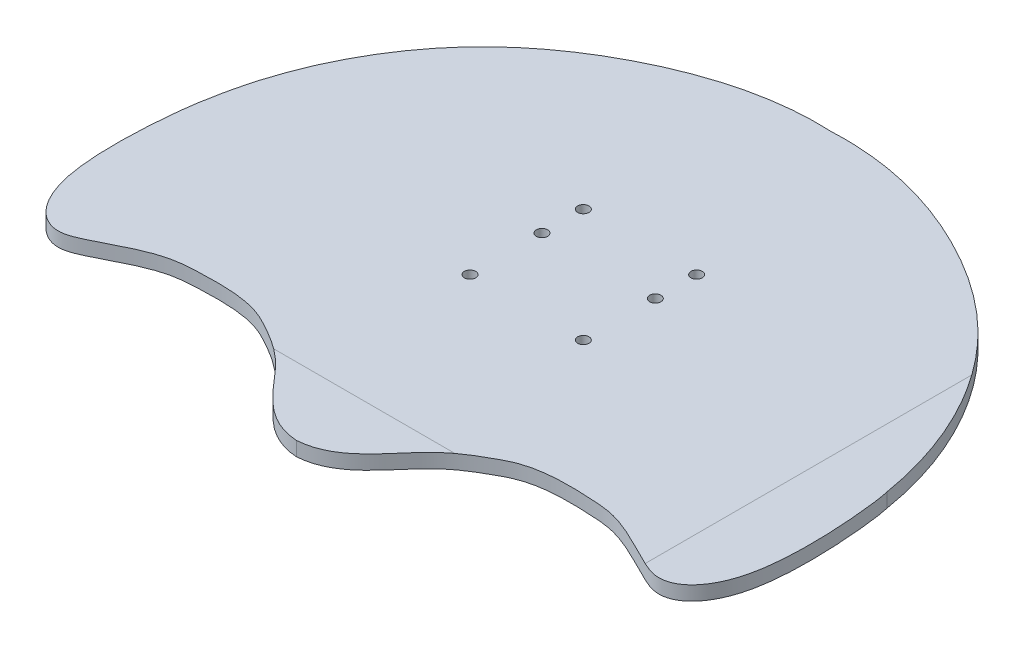
SolidWorks part; units mm, degrees
material "6061-T6 (SS)"
ref_plane "Front Plane" through (0, 0, 0) normal (0, 0, 1) x (1, 0, 0)
ref_plane "Top Plane" through (0, 0, 0) normal (0, 1, 0) x (1, 0, 0)
ref_plane "Right Plane" through (0, 0, 0) normal (1, 0, 0) x (0, 0, -1)
sketch "Sketch3" plane through (0, 0, 0) normal (0, 1, 0) x (1, 0, 0)
  line L0 (0, 0) -> (0, 159.1899) construction
  line L1 (0, 0) -> (0, -140.5301) construction
  line L2 (0, 0) -> (-190.5, 0) construction
  line L3 (0, 0) -> (190.5, 0) construction
  spline S0 degree 3 poles (-190.5, 0) (-184.3927, 37.537) (-157.2613, 93.9641) (-82.3875, 146.6227) (-31.3114, 160.7999) (0, 159.1899) knots 0 0 0 0 0.424401 0.65637 1 1 1 1
  spline S1 degree 3 poles (-190.5, 0) (-192.064, -4.9635) (-201.9672, -83.3146) (-174.6966, -109.29) (-151.6301, -100.568) (-131.4108, -87.7198) (-96.8436, -85.3754) (-78.6925, -86.2588) (-58.8335, -96.8794) (-37.3059, -109.9358) (-21.3496, -139.1148) (0, -140.5301) knots 0 0 0 0 0.166997 0.292321 0.319633 0.426735 0.458914 0.609242 0.64191 0.766802 1 1 1 1
  spline S2 degree 3 poles (190.5, 0) (192.064, -4.9635) (201.9672, -83.3146) (174.6966, -109.29) (151.6301, -100.568) (131.4108, -87.7198) (96.8436, -85.3754) (78.6925, -86.2588) (58.8335, -96.8794) (37.3059, -109.9358) (21.3496, -139.1148) (0, -140.5301) knots 0 0 0 0 0.166997 0.292321 0.319633 0.426735 0.458914 0.609242 0.64191 0.766802 1 1 1 1
  spline S3 degree 3 poles (190.5, 0) (184.3927, 37.537) (157.2613, 93.9641) (82.3875, 146.6227) (31.3114, 160.7999) (0, 159.1899) knots 0 0 0 0 0.424401 0.65637 1 1 1 1
  dimension "D1" = 381
  dimension "D2" = 299.72
  dimension "D3" = 159.1899
  dimension "D4" = 86.8953
  dimension "D5" = 104.4979
  dimension "D6" = 29.1616
  dimension "D7" = 92.2742
  dimension "D8" = 108.411
  dimension "D9" = 67.4883
  dimension "D10" = 43.7314
  dimension "D11" = 117.6915
  dimension "D12" = 162.2568
  dimension "D13" = 89.4522
  dimension "D14" = 140.1036
  dimension "D15" = 175.0666
  dimension "D16" = 50.2669
  dimension "D17" = 101.3666
  dimension "D18" = 138.1225
  dimension "D19" = 155.1557
  dimension "D20" = 192.0074
  dimension "D21" = 193.9268
  dimension "D23" = 76.6666
extrude "Boss-Extrude1" add sketch "Sketch3" along normal blind 7.9502 from surface starting at plane "Top Plane"
sketch "Sketch5" plane through (0, 0, 0) normal (0, -1, 0) x (1, 0, 0)
  line L0 (0, 0) -> (0, -20.32) construction
  line L1 (31.75, -52.07) -> (-31.75, -52.07)
  line L2 (31.75, -52.07) -> (31.75, 11.43)
  line L3 (31.75, 11.43) -> (-31.75, 11.43)
  line L4 (-31.75, -52.07) -> (-31.75, 11.43)
  line L5 (31.75, -52.07) -> (-31.75, 11.43) construction
  line L6 (31.75, 11.43) -> (-31.75, -52.07) construction
  line L7 (-31.75, -52.07) -> (-31.75, -28.8925)
  line L8 (-31.75, -28.8925) -> (31.75, -28.8925) construction
  point P0 (0, -20.32)
  point P3 (0, -20.32)
  dimension "D2" = 63.5
  dimension "D3" = 63.5
  dimension "D4" = 23.1775
hole_wizard "1/4 (0.25) Diameter Hole1" positions "Sketch6" profile "Sketch7" hole size "1/4" standard "ANSI Inch" end condition through all
sketch "Sketch6" plane through (0, 0, 0) normal (0, -1, 0) x (-1, 0, 0)
  point P0 (-31.75, 52.07)
  point P3 (31.75, 52.07)
  point P6 (31.75, -11.43)
  point P9 (-31.75, -11.43)
  point P12 (-31.75, 28.8925)
  point P15 (31.75, 28.8925)
sketch "Sketch7" plane through (31.75, 0, -52.07) normal (1, 0, 0) x (0, 0, -1)
  line L0 (0, 0) -> (0, 7.9502)
  line L1 (0, 7.9502) -> (3.175, 7.9502)
  line L2 (3.175, 7.9502) -> (3.175, 0)
  line L5 (3.175, 0) -> (0, 0)
  line L11 (0, -6.35) -> (0, 107.95) construction
  dimension "Thru Hole Dia." = 6.35
  dimension "Thru Hole Depth" = 7.9502
sketch "Sketch9" plane through (0, 7.9502, 0) normal (0, 1, 0) x (1, 0, 0)
  line L0 (157.5201, -102.5466) -> (157.5201, 80.5195)
  line L1 (-50.7649, -102.4301) -> (50.7649, -102.4301)
  spline S0 degree 3 poles (0, -140.5301) (21.3496, -139.1148) (37.3059, -109.9358) (58.8335, -96.8794) (78.6925, -86.2588) (96.8436, -85.3754) (131.4108, -87.7198) (151.6301, -100.568) (174.6966, -109.29) (201.9672, -83.3146) (192.064, -4.9635) (190.5, 0) knots 0 0 0 0 0.233198 0.35809 0.390758 0.541086 0.573265 0.680367 0.707679 0.833003 1 1 1 1 construction
  spline S1 degree 3 poles (190.5, 0) (184.3927, 37.537) (157.2613, 93.9641) (82.3875, 146.6227) (31.3114, 160.7999) (0, 159.1899) knots 0 0 0 0 0.424401 0.65637 1 1 1 1 construction
  spline S2 degree 3 poles (-190.5, 0) (-192.064, -4.9635) (-201.9672, -83.3146) (-174.6966, -109.29) (-151.6301, -100.568) (-131.4108, -87.7198) (-96.8436, -85.3754) (-78.6925, -86.2588) (-58.8335, -96.8794) (-37.3059, -109.9358) (-21.3496, -139.1148) (0, -140.5301) knots 0 0 0 0 0.166997 0.292321 0.319633 0.426735 0.458914 0.609242 0.64191 0.766802 1 1 1 1 construction
  dimension "D1" = 38.1
split line "Split Line1"
equation "\"Plate thickness\"=0.313"
equation "\"D1@Boss-Extrude1\"=\"Plate thickness\""
equation "\"Bracket Alignment\"= .80"
equation "\"D1@Sketch5\"=\"Bracket Alignment\""
